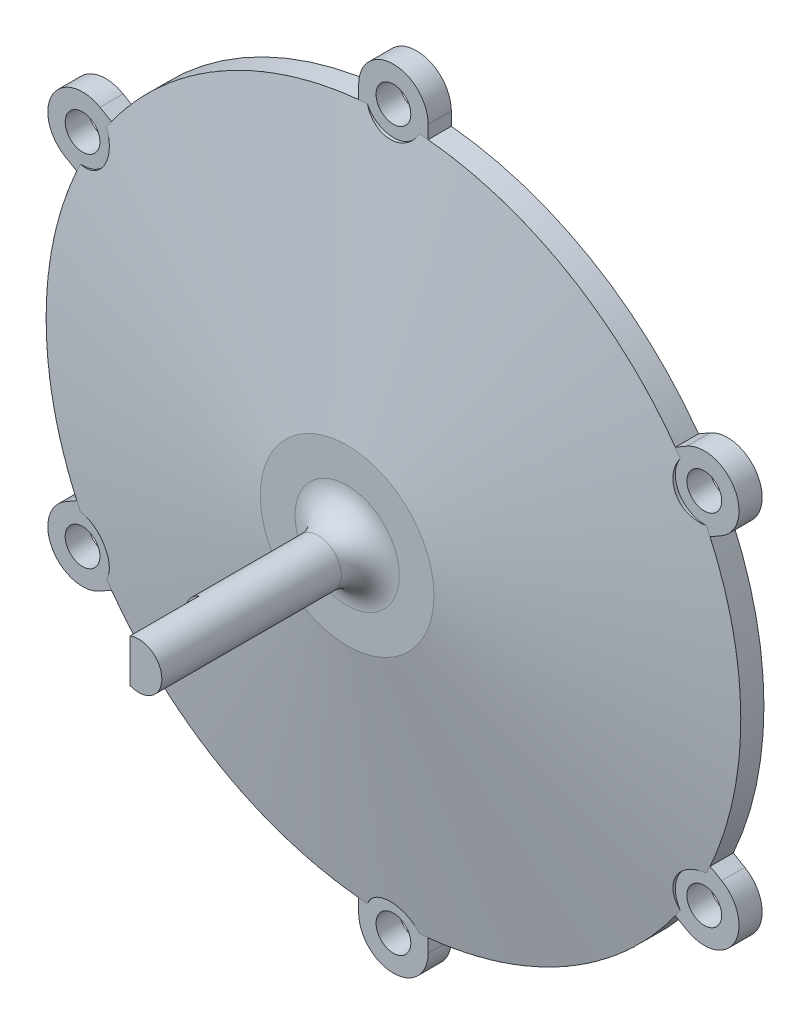
SolidWorks part; units mm, degrees
ref_plane "Front Plane" through (0, 0, 0) normal (0, 0, 1) x (1, 0, 0)
ref_plane "Top Plane" through (0, 0, 0) normal (0, 1, 0) x (1, 0, 0)
ref_plane "Right Plane" through (0, 0, 0) normal (1, 0, 0) x (0, 0, -1)
sketch "Sketch1" plane through (0, 0, 0) normal (0, 0, 1) x (1, 0, 0)
  line L0 (-6, 62) -> (-6, 59.6992)
  line L1 (6, 62) -> (6, 59.6992)
  line L2 (50.6936, 36.1962) -> (48.7011, 35.0458)
  line L3 (56.6936, 25.8038) -> (54.7011, 24.6535)
  line L4 (56.6936, -25.8038) -> (54.7011, -24.6535)
  line L5 (50.6936, -36.1962) -> (48.7011, -35.0458)
  line L6 (6, -62) -> (6, -59.6992)
  line L7 (-6, -62) -> (-6, -59.6992)
  line L8 (-50.6936, -36.1962) -> (-48.7011, -35.0458)
  line L9 (-56.6936, -25.8038) -> (-54.7011, -24.6535)
  line L10 (-56.6936, 25.8038) -> (-54.7011, 24.6535)
  line L11 (-50.6936, 36.1962) -> (-48.7011, 35.0458)
  line L12 (0, 0) -> (6, 59.6992) construction
  circle A0 centre (0, 0) radius 57
  circle A1 centre (0, 0) radius 60
  arc A2 (6, 62) -> (-6, 62) centre (0, 62) ccw
  arc A3 (56.6936, 25.8038) -> (50.6936, 36.1962) centre (53.6936, 31) ccw
  arc A4 (50.6936, -36.1962) -> (56.6936, -25.8038) centre (53.6936, -31) ccw
  arc A5 (-6, -62) -> (6, -62) centre (0, -62) ccw
  arc A6 (-56.6936, -25.8038) -> (-50.6936, -36.1962) centre (-53.6936, -31) ccw
  arc A7 (-50.6936, 36.1962) -> (-56.6936, 25.8038) centre (-53.6936, 31) ccw
  dimension "D1" = 120
  dimension "D2" = 3
  dimension "D3" = 6
  dimension "D4" = 62
  dimension "D5" = 6
extrude "Boss-Extrude1" add sketch "Sketch1" along normal blind 4 contours L11 A7 L10 A1 | L1 A2 L0 A1 | L3 A3 L2 A1 | L5 A4 L4 A1 | L7 A5 L6 A1 | L9 A6 L8 A1 | A0 A1 region at (0, 63.4372, 0) region at (0, 58.3029, 0) region at (-54.9382, 31.7186, 0) region at (54.9382, 31.7186, 0) region at (-54.9382, -31.7186, 0) region at (54.9382, -31.7186, 0) region at (0, -63.4372, 0)
sketch "Sketch3" plane through (0, 0, 0) normal (0, 1, 0) x (1, 0, 0)
  line L0 (0, -4) -> (60, -4)
  line L1 (-6, -4) -> (6, -4) construction
  line L2 (60, -4) -> (15, -12)
  line L3 (15, -12) -> (0, -12)
  line L4 (0, -12) -> (0, -4)
  line L5 (48.7011, 0) -> (6, 0) construction
  line L6 (48.7011, 0) -> (6, 0) construction
  line L7 (0, -4) -> (60, -4)
  line L8 (0, -4) -> (0, -0.5)
  line L9 (0, -0.5) -> (57, -0.5)
  line L13 (57, -0.5) -> (57, -4)
  line L15 (-57, -4) -> (57, -4) construction
  dimension "D1" = 12
  dimension "D2" = 15
  dimension "D3" = 0.5
  dimension "D4" = 3
revolve "Revolve1" add sketch "Sketch3" angle 360 about L4 region at (28.5, 0, 2.25) region at (21, 0, 7.2)
sketch "Sketch4" plane through (0, 0, 0.5) normal (0, 0, 1) x (1, 0, 0)
  circle A0 centre (0, 0) radius 14
  dimension "D1" = 28
extrude "Cut-Extrude1" cut sketch "Sketch4" along normal blind 7 contours A0
sketch "Sketch9" plane through (0, 0, 7.5) normal (0, 0, -1) x (-1, 0, 0)
  circle A0 centre (0, 0) radius 11.5
  dimension "D1" = 23
extrude "Cut-Extrude4" cut sketch "Sketch9" against normal blind 0.5
sketch "Sketch10" plane through (0, 0, 12) normal (0, 0, 1) x (1, 0, 0)
  circle A0 centre (0, 0) radius 4
  dimension "D1" = 8
extrude "Boss-Extrude2" add sketch "Sketch10" along normal blind 36
fillet "Fillet1" radius 5 1 edges at (4, 0, 12)
sketch "Sketch7" plane through (0, 0, 4) normal (0, 0, 1) x (1, 0, 0)
  circle A0 centre (0, 62) radius 3
  arc A1 (6, 62) -> (-6, 62) centre (0, 62) ccw construction
  dimension "D1" = 6
extrude "Cut-Extrude2" cut sketch "Sketch7" against normal through all
sketch "Sketch8" plane through (0, 0, 4) normal (0, 0, 1) x (1, 0, 0)
  circle A0 centre (0, 62) radius 5
  dimension "D1" = 10
extrude "Cut-Extrude3" cut sketch "Sketch8" along normal through all
pattern_circular "CirPattern6" count 6 over 360 about axis through (0, 0, 4) along (0, 0, 1) of "Cut-Extrude2", "Cut-Extrude3"
sketch "Sketch11" plane through (0, 0, 48) normal (0, 0, 1) x (1, 0, 0)
  line L1 (-1.5, 3.7081) -> (-4, 3.7081)
  line L2 (-1.5, 3.7081) -> (-1.5, -3.7081)
  line L3 (-1.5, -3.7081) -> (-4, -3.7081)
  line L4 (-4, 3.7081) -> (-4, -3.7081)
  circle A0 centre (0, 0) radius 4 construction
  dimension "D1" = 2.5
extrude "Cut-Extrude5" cut sketch "Sketch11" against normal blind 12
